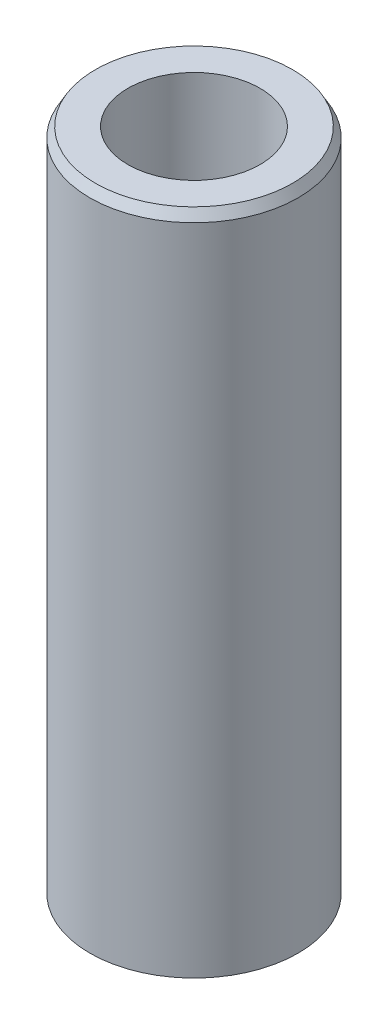
SolidWorks part; units mm, degrees
ref_plane "Front Plane" through (0, 0, 0) normal (0, 0, 1) x (1, 0, 0)
ref_plane "Top Plane" through (0, 0, 0) normal (0, 1, 0) x (1, 0, 0)
ref_plane "Right Plane" through (0, 0, 0) normal (1, 0, 0) x (0, 0, -1)
sketch "Sketch1" plane through (0, 0, 0) normal (0, 1, 0) x (1, 0, 0)
  circle A0 centre (0, 0) radius 47.5
  dimension "SHAFT_OD" = 95
extrude "Boss-Extrude1" add sketch "Sketch1" along normal blind 305.4041
sketch "Sketch2" plane through (0, 0, 0) normal (0, 1, 0) x (1, 0, 0)
  circle A0 centre (0, 0) radius 30.163
  dimension "BORE_D" = 60.326
extrude "Cut-Extrude1" cut sketch "Sketch2" along normal through all
chamfer "Chamfer1" distance 4.4681 angle 29.714 2 edges at (0, 305.4041, 47.5) (0, 0, 47.5) first distance on face at (0, 305.4041, 47.5) first distance on face at (0, 0, 30.163)
